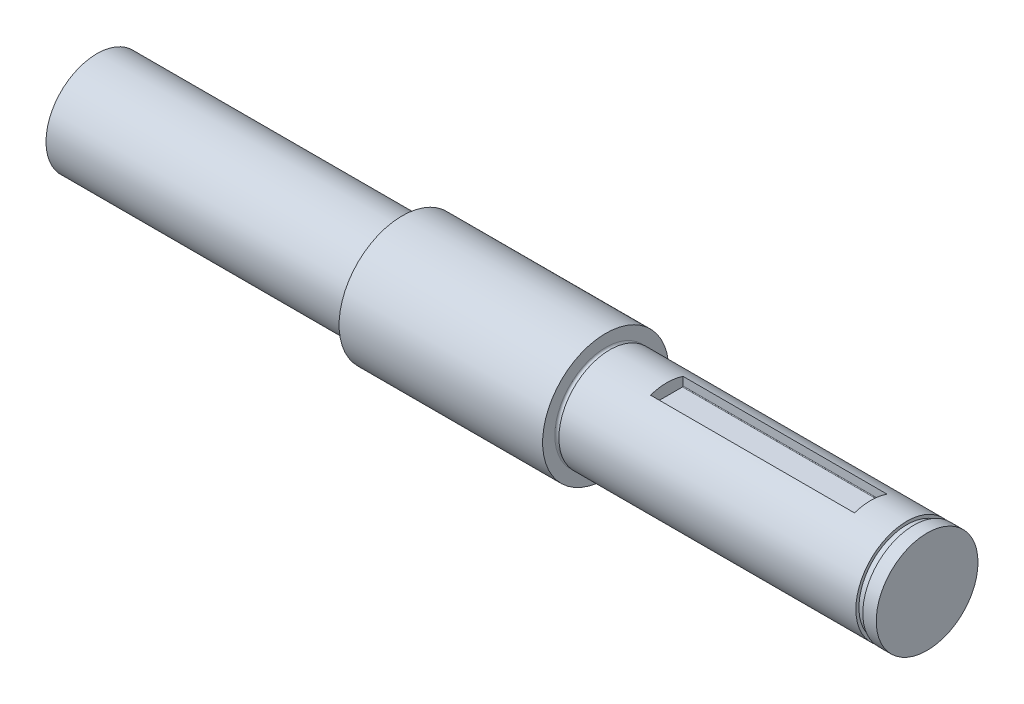
SolidWorks part; units mm, degrees
ref_plane "Front Plane" through (0, 0, 0) normal (0, 0, 1) x (1, 0, 0)
ref_plane "Top Plane" through (0, 0, 0) normal (0, 1, 0) x (1, 0, 0)
ref_plane "Right Plane" through (0, 0, 0) normal (1, 0, 0) x (0, 0, -1)
sketch "Sketch1" plane through (0, 0, 0) normal (1, 0, 0) x (0, 0, -1)
  circle A0 centre (0, 0) radius 25
  circle A1 centre (0, 0) radius 31
  dimension "D1" = 50
  dimension "D2" = 62
extrude "Boss-Extrude1" add sketch "Sketch1" along normal mid plane 100 contours A0 | A1 A0 region at (0, 0, 0) region at (0, 0, 30.1232)
extrude "Boss-Extrude2" add sketch "Sketch1<4>" along normal mid plane 400 contours A0 region at (0, 0, 0)
sketch "Sketch1<4>" plane through (0, 0, 0) normal (1, 0, 0) x (0, 0, -1) same geometry as "Sketch1"
sketch "Sketch3" plane through (0, 0, 0) normal (0, 0, 1) x (1, 0, 0)
  line L0 (200, 25) -> (50, 25) construction
  line L1 (50, -31) -> (50, 31) construction
  line L2 (52, 25) -> (50, 25)
  line L3 (0, 0) -> (63.2185, 0) construction
  line L4 (0, 0) -> (0, 26.6824) construction
  line L5 (-52, 25) -> (-50, 25)
  arc A0 (52, 25) -> (50, 25) centre (51, 25) cw
  arc A1 (-52, 25) -> (-50, 25) centre (-51, 25) ccw
  dimension "D1" = 1
  dimension "D2" = 2
revolve "Cut-Revolve1" cut sketch "Sketch3" angle 360 about L3
sketch "Sketch4" plane through (50, 0, 0) normal (1, 0, 0) x (0, 0, -1)
  line L0 (-8, 23.6854) -> (-8, 19.6)
  line L1 (-7.7, 19.3) -> (7.7, 19.3)
  line L2 (8, 19.6) -> (8, 23.6854)
  circle A0 centre (0, 0) radius 25 construction
  arc A1 (8, 23.6854) -> (-8, 23.6854) centre (0, 0) ccw
  arc A2 (-8, 19.6) -> (-7.7, 19.3) centre (-7.7, 19.6) ccw
  arc A3 (7.7, 19.3) -> (8, 19.6) centre (7.7, 19.6) ccw
  point P7 (0, 19.3)
  point P9 (0, 25)
  point P12 (-8, 19.3)
  point P15 (8, 19.3)
  dimension "D1" = 16
  dimension "D3" = 0.3
  dimension "D2" = 5.7
extrude "Cut-Extrude1" cut sketch "Sketch4" along normal blind 100.215 from offset 30
sketch "Sketch5" plane through (200, 0, 0) normal (1, 0, 0) x (0, 0, -1)
  circle A0 centre (0, 0) radius 25
  dimension "D1" = 50
extrude "Boss-Extrude3" add sketch "Sketch5" along normal blind 7.91
sketch "Sketch6" plane through (207.91, 0, 0) normal (1, 0, 0) x (0, 0, -1)
  circle A0 centre (0, 0) radius 25
  circle A1 centre (0, 0) radius 23.5
  dimension "D1" = 50
  dimension "D2" = 47
extrude "Cut-Extrude2" cut sketch "Sketch6" along normal blind 3.4 from offset 10 offset against normal yes
